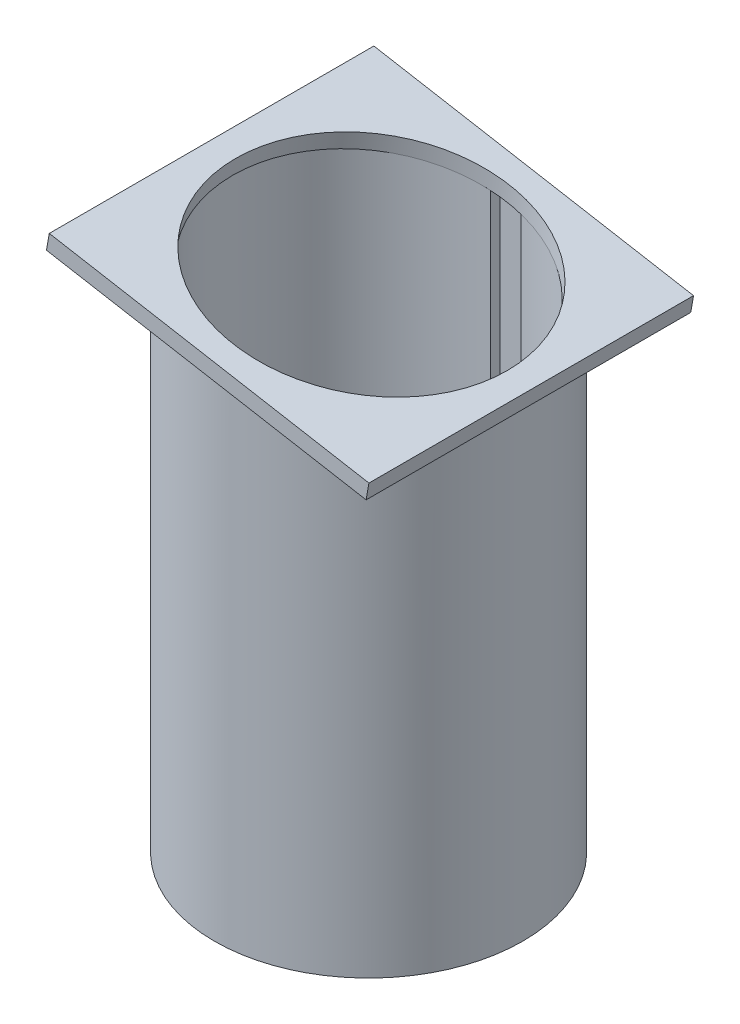
SolidWorks part; units mm, degrees
ref_plane "Front Plane" through (0, 0, 0) normal (0, 0, 1) x (1, 0, 0)
ref_plane "Top Plane" through (0, 0, 0) normal (0, 1, 0) x (1, 0, 0)
ref_plane "Right Plane" through (0, 0, 0) normal (1, 0, 0) x (0, 0, -1)
ref_axis "Axis2" through (0, 0, 52.25) along (0, 0, -1)
ref_plane "Plane8" through (0, 0, 0) normal (0.1736, 0.9848, 0) x (0, 0, -1)
ref_plane "Plane9" through (26.0472, 147.7212, 0) normal (0.1736, 0.9848, 0) x (0, 0, -1)
sketch "Sketch1" plane through (0, 0, 0) normal (0, 1, 0) x (1, 0, 0)
  line L0 (0, 42.5) -> (0, -42.5) construction
  line L1 (-4.75, -42.2337) -> (-4.75, -45.2337)
  line L2 (-4.75, -45.2337) -> (4.75, -45.2337)
  line L3 (4.75, -42.2337) -> (4.75, -45.2337)
  line L4 (-42.5, 0) -> (42.5, 0) construction
  line L5 (4.75, 42.2337) -> (4.75, 45.2337)
  line L6 (-4.75, 45.2337) -> (4.75, 45.2337)
  line L7 (-4.75, 42.2337) -> (-4.75, 45.2337)
  circle A0 centre (0, 0) radius 47.5
  arc A1 (-4.75, 42.2337) -> (-4.75, -42.2337) centre (0, 0) ccw
  arc A2 (4.75, -42.2337) -> (4.75, 42.2337) centre (0, 0) ccw
  dimension "D2" = 95
  dimension "D1" = 85
  dimension "D3" = 9.5
  dimension "D4" = 3
  dimension "D5" = 4.75
sketch "Sketch2" plane through (0, 0, 0) normal (0, 1, 0) x (1, 0, 0)
  line L0 (0, 0) -> (0, -37.5) construction
  circle A0 centre (0, 0) radius 47.5
  circle A1 centre (0, 0) radius 37.5
  dimension "D2" = 95
  dimension "D1" = 75
extrude "Boss-Extrude2" add sketch "Sketch2" along normal blind 5
extrude "Boss-Extrude4" add sketch "Sketch1" along normal up to surface (152.314 mm away) up to plane "Plane9"
sketch "Sketch9" plane through (26.0472, 147.7212, 0) normal (0.1736, 0.9848, 0) x (0, 0, -1)
  line L1 (50, 76.449) -> (-50, 76.449)
  line L2 (50, 76.449) -> (50, -23.551)
  line L3 (50, -23.551) -> (-50, -23.551)
  line L4 (-50, 76.449) -> (-50, -23.551)
  line L5 (50, 76.449) -> (-50, -23.551) construction
  line L6 (50, -23.551) -> (-50, 76.449) construction
  circle A0 centre (0, 26.449) radius 42.5
  point P6 (0, 0)
  dimension "D1" = 100
  dimension "D2" = 100
extrude "Boss-Extrude7" add sketch "Sketch9" along normal blind 5
equation "\"BallBearingDiameter\" = 22mm"
equation "\"SmallTubeOD\" = 75mm"
equation "\"SmallTubeID\"= \"SmallTubeOD\" - \"WallThickness\" * 2"
equation "\"ZTravel\"= 20mm"
equation "\"WallThickness\"= 5mm"
equation "\"D1@Boss-Extrude1\"= \"ZTravel\""
equation "\"D1@Sketch4\"=\"SmallTubeID\""
equation "\"RestrictingFlangeOD\"= \"SmallTubeOD\" + 10mm"
equation "\"D2@Sketch4\"=\"RestrictingFlangeOD\""
equation "\"D1@Boss-Extrude3\"=\"WallThickness\""
equation "\"HexNutDiameter\" = 13mm"
equation "\"D1@Sketch7\"=\"HexNutDiameter\""
equation "\"D3@Sketch4\"=\"HexNutDiameter\"+5"
equation "\"D2@Sketch1\"=\"SmallTubeOD\"+20"
equation "\"D2@Sketch2\"=\"SmallTubeOD\"+20"
equation "\"D1@Sketch2\"=\"SmallTubeOD\""
equation "\"D1@Sketch1\"=\"SmallTubeOD\"+10"
